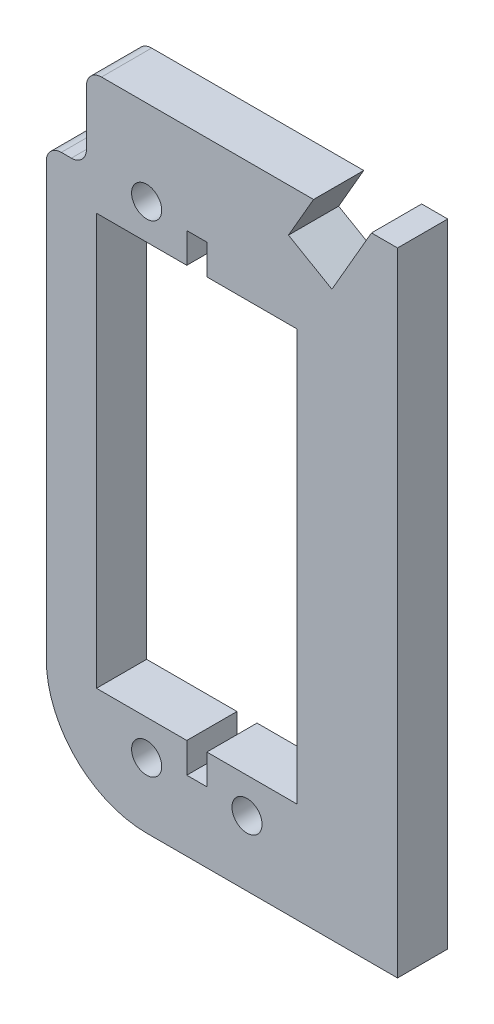
SolidWorks part; units mm, degrees
ref_plane "Plan de face" through (0, 0, 0) normal (0, 0, 1) x (1, 0, 0)
ref_plane "Plan de dessus" through (0, 0, 0) normal (0, 1, 0) x (1, 0, 0)
ref_plane "Plan de droite" through (0, 0, 0) normal (1, 0, 0) x (0, 0, -1)
sketch "Esquisse1" plane through (0, 0, 0) normal (0, 0, 1) x (1, 0, 0)
  line L0 (15, 10) -> (15, 51) construction
  line L1 (0, 0) -> (25, 0)
  line L2 (0, 0) -> (0, 54.5)
  line L3 (4, 63) -> (15, 63)
  line L4 (32.4055, 63) -> (28.4621, 56.1699)
  line L5 (14, 51) -> (5, 51)
  line L6 (15, 63) -> (26.632, 63)
  line L7 (25, 10) -> (16, 10)
  line L8 (5, 51) -> (5, 10)
  line L9 (5, 30.5) -> (25, 30.5) construction
  line L10 (25, 10) -> (25, 51)
  line L11 (25, 51) -> (16, 51)
  line L12 (25, 0) -> (35, 0)
  line L13 (35, 0) -> (35, 63)
  line L14 (31.0278, 60.6138) -> (27.2778, 54.1186) construction
  line L15 (28.4621, 56.1699) -> (24.132, 58.6699)
  line L16 (24.132, 58.6699) -> (26.632, 63)
  line L17 (32.4055, 63) -> (35, 63)
  line L18 (16, 10) -> (16, 7)
  line L19 (14, 10) -> (5, 10)
  line L20 (14, 51) -> (14, 54)
  line L21 (14, 54) -> (16, 54)
  line L22 (16, 51) -> (16, 54)
  line L23 (14, 7) -> (16, 7)
  line L24 (14, 10) -> (14, 7)
  line L28 (0, 54.5) -> (4, 54.5)
  line L29 (4, 63) -> (4, 54.5)
  circle A0 centre (10, 54.5) radius 1.5
  circle A1 centre (20, 54.5) radius 1.5 construction
  circle A2 centre (20, 6.5) radius 1.5
  circle A3 centre (10, 6.5) radius 1.5
  dimension "D6" = 3.5
  dimension "D8" = 3
  dimension "D1" = 20
  dimension "D2" = 41
  dimension "D3" = 10
  dimension "D4" = 12
  dimension "D5" = 5
  dimension "D7" = 5
  dimension "D9" = 10
  dimension "D10" = 5
  dimension "D11" = 5
  dimension "D12" = 2
  dimension "D13" = 3
  dimension "D14" = 8.5
  dimension "D15" = 4
extrude "Boss.-Extru.1" add sketch "Esquisse1" along normal blind 5
fillet "Congé2" radius 10 1 edges at (0, 0, 2.5)
fillet "Congé3" radius 1.5 3 edges at (4, 63, 2.5) (4, 54.5, 2.5) (0, 54.5, 2.5)
